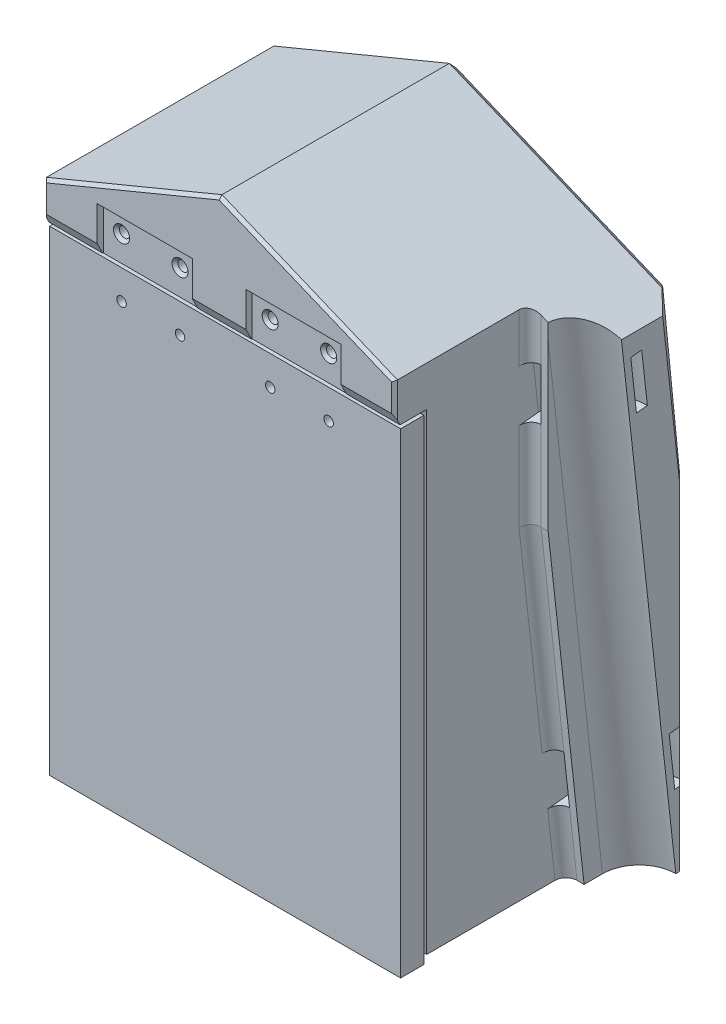
SolidWorks part; units mm, degrees
other "Door"
other "House"
other "Cover" parameters "D1"=134.3446, "D2"=7.568, "D3"=4.0473, "D4"=11.5
ref_plane "Front Plane" through (0, 0, 0) normal (0, 0, 1) x (1, 0, 0)
ref_plane "Top Plane" through (0, 0, 0) normal (0, 1, 0) x (1, 0, 0)
ref_plane "Right Plane" through (0, 0, 0) normal (1, 0, 0) x (0, 0, -1)
sketch "Sketch1" plane through (0, 0, 0) normal (0, 0, 1) x (1, 0, 0)
  line L0 (-48, 73.5589) -> (-48, -66.5589)
  line L1 (-45, -61.5589) -> (45, -61.5589)
  line L2 (-45, -61.5589) -> (-45, 61.5589)
  line L3 (-45, 61.5589) -> (45, 61.5589)
  line L4 (45, -61.5589) -> (45, 61.5589)
  line L5 (0, 61.5589) -> (0, -61.5589) construction
  line L6 (-45, 0) -> (45, 0) construction
  line L7 (-48, -66.5589) -> (48, -66.5589)
  line L8 (48, -66.5589) -> (48, 73.5589)
  line L9 (48, 73.5589) -> (0, 93.4411)
  line L10 (0, 93.4411) -> (-48, 73.5589)
  point P0 (0, 0)
  dimension "D1" = 160
  dimension "D2" = 90
  dimension "D3" = 22.5
  dimension "D4" = 12
  dimension "D5" = 5
  dimension "D6" = 3
  dimension "D7" = 123.1177
extrude "main-extrude" add sketch "Sketch1" along normal blind 60
sketch "Sketch2" plane through (0, 0, 0) normal (0, 0, 1) x (1, 0, 0)
  line L0 (48, -66.5589) -> (48, 73.5589) construction
  line L1 (-48, -66.5589) -> (48, -66.5589) construction
  line L2 (-48, 73.5589) -> (-48, -66.5589) construction
  line L3 (48, 73.5589) -> (0, 93.4411) construction
  line L4 (0, 93.4411) -> (-48, 73.5589) construction
  line L5 (48, -66.5589) -> (48, 73.5589)
  line L6 (-48, -66.5589) -> (48, -66.5589)
  line L7 (-48, 73.5589) -> (-48, -66.5589)
  line L8 (48, 73.5589) -> (0, 93.4411)
  line L9 (0, 93.4411) -> (-48, 73.5589)
extrude "rear-extrude" add sketch "Sketch2" against normal blind 5
sketch "Sketch6" plane through (0, -66.5589, 0) normal (0, -1, 0) x (1, 0, 0)
  line L0 (48, 22.9375) -> (52, 22.9375)
  line L1 (62.9375, 15) -> (62.9375, 22.9375)
  line L2 (52, 22.9375) -> (55, 22.9375)
  line L3 (-48, -5) -> (48, -5) construction
  line L4 (62.9375, 15) -> (62.9375, -5)
  line L5 (62.9375, -5) -> (48, -5)
  line L6 (48, 60) -> (48, -5) construction
  line L7 (48, -5) -> (48, 22.9375)
  line L8 (62.9375, 22.9375) -> (55, 22.9375)
  circle A0 centre (62.9375, 22.9375) radius 7.9375 construction
  arc A1 (62.9375, 15) -> (55, 22.9375) centre (62.9375, 22.9375) cw construction
  point P3 (62.9375, 15)
  dimension "D3" = 15.875
  dimension "D1" = 4
  dimension "D2" = 3
  dimension "D4" = 20
extrude "Boss-Extrude3" add sketch "Sketch6" against normal up to surface (140.1177 mm away) up to face at (24, 83.5, 27.5)
sketch "Sketch19" plane through (62.9375, 0, 0) normal (1, 0, 0) x (0, 0, -1)
  line L0 (-7.4977, -71.6348) -> (-21.3388, 52.9783) construction
  line L2 (-22.9375, 67.3716) -> (-32.8764, 66.2676) construction
  line L3 (-7.9389, -67.6628) -> (2, -66.5589) construction
  line L6 (5, -66.5589) -> (-22.9375, -66.5589) construction
  dimension "D1" = 10
  dimension "D3" = 3
ref_plane "Plane6" through (62.9375, -67.6628, 7.9389) normal (0, 0.9939, 0.1104) x (1, 0, 0)
sketch "Sketch20" plane through (62.9375, -67.6628, 7.9389) normal (0, 0.9939, 0.1104) x (1, 0, 0)
  line L0 (10, 0) -> (10, -24.5702)
  line L3 (10, -24.5702) -> (-14.9375, -24.5702)
  line L4 (21.2132, 0) -> (-21.2132, 42.4264)
  line L5 (-21.2132, 42.4264) -> (21.2132, 42.4264)
  line L6 (21.2132, 42.4264) -> (21.2132, 0)
  line L7 (0, 0) -> (10.6066, 10.6066) construction
  line L8 (-10, 0) -> (-10, -5)
  line L9 (-10, -5) -> (-14.9375, -5)
  line L10 (-14.9375, -5) -> (-14.9375, -24.5702)
  circle A0 centre (0, 0) radius 10 construction
  circle A3 centre (0, 0) radius 15 construction
  arc A4 (-10, 0) -> (10, 0) centre (0, 0) cw
  point P16 (10.6066, 10.6066)
  point P18 (10.6066, 10.6066)
  point P19 (10.6066, 10.6066)
  point P20 (10.6066, 10.6066)
  point P21 (10.6066, 10.6066)
  point P22 (7.0711, 7.0711)
  dimension "D1" = 20
  dimension "D2" = 5
  dimension "D3" = 5
extrude "Cut-Extrude9" cut sketch "Sketch20" along normal through all
ref_plane "Plane1" through (62.9375, -47.7851, 10.1468) normal (0, 0.9939, 0.1104) x (1, 0, 0)
ref_plane "Plane2" through (0, 0, 0) normal (0, 0.9939, 0.1104) x (1, 0, 0)
sketch "Sketch7" plane through (62.9375, -47.7851, 10.1468) normal (0, 0.9939, 0.1104) x (1, 0, 0)
  line L0 (-14.9375, -15) -> (-11.9375, -15)
  line L2 (-14.9375, -5) -> (-10, -5) construction
  line L4 (-11.9375, -15) -> (-11.9375, -5)
  line L5 (-11.9375, -5) -> (-11.9375, 0)
  line L6 (-14.9375, -15) -> (-14.9375, 0)
  line L7 (0, 11.9375) -> (10, 11.9375)
  line L8 (10, 11.9375) -> (10, 14.9375)
  line L9 (10, 14.9375) -> (0, 14.9375)
  line L10 (-14.9375, -51.6211) -> (-14.9375, -5) construction
  arc A2 (-11.9375, 0) -> (0, 11.9375) centre (0, 0) cw
  arc A3 (0, 14.9375) -> (-14.9375, 0) centre (0, 0) ccw
  circle A4 centre (0, 0) radius 10 construction
  dimension "D1" = 3
  dimension "D2" = 10
  dimension "D3" = 10
extrude "Cut-Extrude10" cut sketch "Sketch7" along normal blind 14
pattern_linear "LPattern1" count 2 spacing 95 along (0, 0.9939, 0.1104) of "Cut-Extrude10"
fillet "Fillet2" radius 3 4 edges at (48, 67.0117, 22.9375) (48, 34.2288, 22.9375) (48, -57.4479, 14.1042) (48, -6.1717, 19.7996)
sketch "Sketch9" plane through (0, -66.5589, 0) normal (0, -1, 0) x (1, 0, 0)
  line L0 (-48, 0) -> (48, 0) construction
  line L3 (-30, 3) -> (0, 3) construction
  line L4 (0, 3) -> (30, 3) construction
  circle A0 centre (-30, 3) radius 3
  circle A1 centre (0, 3) radius 3
  circle A2 centre (30, 3) radius 3
  dimension "D1" = 6
  dimension "D2" = 30
extrude "inner-drain-holes" cut sketch "Sketch9" against normal blind 15
sketch "Sketch4" plane through (0, 0, 60) normal (0, 0, 1) x (1, 0, 0)
  line L0 (-48, 73.5589) -> (-48, -66.5589) construction
  line L1 (-48, 61.5589) -> (48, 61.5589) construction
  line L2 (-48, 61.5589) -> (-48, -66.5589)
  line L3 (-48, -66.5589) -> (48, -66.5589)
  line L4 (48, 61.5589) -> (48, -66.5589)
  line L5 (48, -66.5589) -> (48, 73.5589) construction
  line L6 (-48, 61.5589) -> (-48, 62.5589)
  line L7 (-48, 73.5589) -> (-48, -66.5589) construction
  line L8 (-48, 62.5589) -> (48, 62.5589)
  line L9 (48, -66.5589) -> (48, 73.5589) construction
  line L10 (48, 62.5589) -> (48, 61.5589)
  dimension "D1" = 1
extrude "Cut-Extrude2" cut sketch "Sketch4" against normal blind 8
sketch "Sketch5" plane through (0, 0, 60) normal (0, 0, 1) x (1, 0, 0)
  line L0 (-33.3333, 61.5589) -> (-7.3333, 61.5589) construction
  line L1 (-33.3333, 48.0589) -> (-7.3333, 48.0589)
  line L2 (-33.3333, 48.0589) -> (-33.3333, 75.0589)
  line L3 (-33.3333, 75.0589) -> (-7.3333, 75.0589)
  line L4 (-7.3333, 48.0589) -> (-7.3333, 75.0589)
  line L5 (-20.3333, 75.0589) -> (-20.3333, 48.0589) construction
  line L6 (-33.3333, 61.5589) -> (-7.3333, 61.5589) construction
  line L7 (-45, 61.5589) -> (45, 61.5589) construction
  line L8 (-48, 61.5589) -> (48, 61.5589) construction
  line L9 (0, -987.8214) -> (0, 49012.1786) construction
  line L10 (-33.3333, 61.5589) -> (-48, 61.5589) construction
  line L11 (-48, 73.5589) -> (-48, -66.5589) construction
  line L12 (33.3333, 75.0589) -> (7.3333, 75.0589)
  line L13 (7.3333, 48.0589) -> (7.3333, 75.0589)
  line L14 (33.3333, 48.0589) -> (7.3333, 48.0589)
  line L15 (33.3333, 48.0589) -> (33.3333, 75.0589)
  line L16 (-7.3333, 61.5589) -> (7.3333, 61.5589) construction
  point P0 (-20.3333, 61.5589)
  dimension "D1" = 27
  dimension "D2" = 26
extrude "Cut-Extrude3" cut sketch "Sketch5" against normal offset from surface (1.65 mm away) 6.35 up to face at (0, 0, 52)
sketch "Sketch15" plane through (0, 0, 58.35) normal (0, 0, 1) x (1, 0, 0)
  line L0 (-28.3333, 69.5589) -> (-12.3333, 69.5589) construction
  line L1 (0, -934.1648) -> (0, 49065.8352) construction
  line L2 (0, -200987.8214) -> (0, 249012.1786) construction
  line L3 (-20.3333, 75.0589) -> (-20.3333, 48.0589) construction
  line L4 (-33.3333, 61.5589) -> (-7.3333, 61.5589) construction
  circle A0 centre (-28.3333, 69.5589) radius 1.4
  circle A1 centre (-12.3333, 69.5589) radius 1.4
  circle A2 centre (28.3333, 69.5589) radius 1.4
  circle A3 centre (12.3333, 69.5589) radius 1.4
  point P8 (-20.3333, 69.5589)
  dimension "D1" = 2.8
  dimension "D2" = 16
  dimension "D3" = 8
extrude "Cut-Extrude7" cut sketch "Sketch15" against normal blind 40
sketch "Sketch12" plane through (0, 0, 52) normal (0, 0, 1) x (1, 0, 0)
  line L5 (0, 61.5589) -> (0, -61.5589) construction
  line L6 (-48.001, 61.5589) -> (48.001, 61.5589)
  line L7 (-48.001, 61.5589) -> (-48.001, -68.5589)
  line L8 (-48.001, -68.5589) -> (48.001, -68.5589)
  line L9 (48.001, 61.5589) -> (48.001, -68.5589)
  line L10 (0, -68.5589) -> (0, 61.5589) construction
  line L11 (-48.001, -3.5) -> (48.001, -3.5) construction
  line L12 (-48, -66.5589) -> (48, -66.5589) construction
  line L13 (-48, 73.5589) -> (-48, -66.5589) construction
  point P0 (0, -3.5)
  dimension "D1" = 2
  dimension "D2" = 0.001
extrude "Boss-Extrude5" add sketch "Sketch12" along normal blind 6.35 separate body
sketch "Sketch13" plane through (0, 0, 58.35) normal (0, 0, 1) x (1, 0, 0)
  line L0 (-1053.3426, 61.5589) -> (48946.6574, 61.5589) construction
  line L1 (-33.3333, 61.5589) -> (-48, 61.5589) construction
  line L4 (7.3333, 48.0589) -> (33.3333, 48.0589)
  line L5 (33.3333, 48.0589) -> (33.3333, 75.0589)
  line L6 (33.3333, 75.0589) -> (7.3333, 75.0589)
  line L7 (7.3333, 75.0589) -> (7.3333, 48.0589)
  line L8 (7.3333, 48.0589) -> (33.3333, 48.0589) construction
  line L9 (33.3333, 48.0589) -> (33.3333, 75.0589) construction
  line L10 (33.3333, 75.0589) -> (7.3333, 75.0589) construction
  line L11 (7.3333, 75.0589) -> (7.3333, 48.0589) construction
  line L12 (-33.3333, 48.0589) -> (-7.3333, 48.0589)
  line L13 (-33.3333, 75.0589) -> (-33.3333, 48.0589)
  line L14 (-7.3333, 75.0589) -> (-33.3333, 75.0589)
  line L15 (-7.3333, 48.0589) -> (-7.3333, 75.0589)
  line L16 (-33.3333, 48.0589) -> (-7.3333, 48.0589) construction
  line L17 (-33.3333, 75.0589) -> (-33.3333, 48.0589) construction
  line L18 (-7.3333, 75.0589) -> (-33.3333, 75.0589) construction
  line L19 (-7.3333, 48.0589) -> (-7.3333, 75.0589) construction
  circle A0 centre (28.3333, 69.5589) radius 1.4 construction
  circle A1 centre (12.3333, 69.5589) radius 1.4 construction
  circle A2 centre (-28.3333, 69.5589) radius 1.4 construction
  circle A3 centre (-12.3333, 69.5589) radius 1.4 construction
  circle A4 centre (28.3333, 69.5589) radius 1.4 construction
  circle A5 centre (12.3333, 69.5589) radius 1.4 construction
  circle A6 centre (-28.3333, 69.5589) radius 1.4 construction
  circle A7 centre (-12.3333, 69.5589) radius 1.4 construction
  circle A8 centre (28.3333, 53.5589) radius 1.4 construction
  circle A9 centre (12.3333, 53.5589) radius 1.4 construction
  circle A10 centre (-12.3333, 53.5589) radius 1.4 construction
  circle A11 centre (-28.3333, 53.5589) radius 1.4 construction
  circle A12 centre (-28.3333, 53.5589) radius 1.3
  circle A13 centre (-12.3333, 53.5589) radius 1.3
  circle A14 centre (12.3333, 53.5589) radius 1.3
  circle A15 centre (28.3333, 53.5589) radius 1.3
  dimension "D3" = 2.6
  dimension "D1" = 0
  dimension "D2" = 0
extrude "Cut-Extrude8" cut sketch "Sketch13" against normal through all
chamfer "Chamfer4" distance 3 distance2 1.5 3 edges at (0, 62.5589, 60) (-40.6667, 62.5589, 60) (40.6667, 62.5589, 60) first distance on face at (0, 70.4729, 60)
chamfer "Chamfer7" distance 0.8 angle 45 4 edges at (26.9333, 69.5589, 58.35) (10.9333, 69.5589, 58.35) (-10.9333, 69.5589, 58.35) (-26.9333, 69.5589, 58.35)
fillet "cavity-fillet" radius 5 4 edges at (45, -61.5589, 26) (-45, -61.5589, 26) (45, 61.5589, 26) (-45, 61.5589, 26)
sketch "Sketch21" plane through (0, 0, 0) normal (0, 0, 1) x (1, 0, 0)
  line L14 (30, -61.0589) -> (40, -61.0589)
  line L15 (44.5, -56.5589) -> (44.5, 56.5589)
  line L16 (40, 61.0589) -> (-40, 61.0589)
  line L17 (-44.5, 56.5589) -> (-44.5, -56.5589)
  line L18 (-40, -61.0589) -> (-30, -61.0589)
  line L19 (-30, -61.0589) -> (0, -61.0589)
  line L20 (0, -61.0589) -> (30, -61.0589)
  line L21 (30, -61.0589) -> (40, -61.0589)
  line L22 (44.5, -56.5589) -> (44.5, 56.5589)
  line L23 (40, 61.0589) -> (-40, 61.0589)
  line L24 (-44.5, 56.5589) -> (-44.5, -56.5589)
  line L25 (-40, -61.0589) -> (-30, -61.0589)
  line L26 (-30, -61.0589) -> (0, -61.0589)
  line L27 (0, -61.0589) -> (30, -61.0589)
  circle A4 centre (-38.5, 55.0589) radius 6 construction
  circle A5 centre (38.5, 55.0589) radius 6 construction
  circle A6 centre (38.5, -55.0589) radius 6 construction
  circle A7 centre (-38.5, -55.0589) radius 6 construction
  arc A8 (40, -61.0589) -> (44.5, -56.5589) centre (40, -56.5589) ccw
  arc A9 (44.5, 56.5589) -> (40, 61.0589) centre (40, 56.5589) ccw
  arc A10 (-40, 61.0589) -> (-44.5, 56.5589) centre (-40, 56.5589) ccw
  arc A11 (-44.5, -56.5589) -> (-40, -61.0589) centre (-40, -56.5589) ccw
  arc A12 (40, -61.0589) -> (44.5, -56.5589) centre (40, -56.5589) ccw
  arc A13 (44.5, 56.5589) -> (40, 61.0589) centre (40, 56.5589) ccw
  arc A14 (-40, 61.0589) -> (-44.5, 56.5589) centre (-40, 56.5589) ccw
  arc A15 (-44.5, -56.5589) -> (-40, -61.0589) centre (-40, -56.5589) ccw
  circle A17 centre (-38.5, 55.0589) radius 1.3
  circle A18 centre (38.5, 55.0589) radius 1.3
  circle A19 centre (-38.5, -55.0589) radius 1.3
  circle A20 centre (38.5, -55.0589) radius 1.3
  dimension "D2" = 12
  dimension "D5" = 2.6
  dimension "D1" = 0.5
  dimension "D3" = 2
  dimension "D4" = 2
extrude "Boss-Extrude10" add sketch "Sketch21" along normal blind 3 separate body
sketch "Sketch22" plane through (0, 0, 0) normal (0, 0, 1) x (1, 0, 0)
  circle A0 centre (-38.5, 55.0589) radius 2
  circle A1 centre (38.5, 55.0589) radius 2
  circle A2 centre (-38.5, -55.0589) radius 2
  circle A3 centre (38.5, -55.0589) radius 2
  circle A4 centre (-38.5, 55.0589) radius 1.3 construction
  circle A5 centre (38.5, 55.0589) radius 1.3 construction
  circle A6 centre (38.5, -55.0589) radius 1.3 construction
  circle A7 centre (-38.5, -55.0589) radius 1.3 construction
  dimension "D1" = 4
extrude "Cut-Extrude11" cut sketch "Sketch22" against normal through all
chamfer "Chamfer6" distance 0.8 angle 45 11 edges at (-45, 0, 52) (-43.5355, 60.0944, 52) (-43.5355, -60.0944, 52) (0, 61.5589, 52) (0, -61.5589, 52) (43.5355, 60.0944, 52) (43.5355, -60.0944, 52) (45, 0, 52) (-48, -2, 52) (48, -2, 52) (0, -66.5589, 52)
chamfer "Chamfer2" distance 2 angle 45 5 edges at (62.9375, -29.2762, -5) (7.4687, -66.5589, -5) (-48, 3.5, -5) (28.035, 81.8287, -5) (-24, 83.5, -5)
chamfer "Chamfer9" distance 0.8 angle 45 4 edges at (-48, 69.5589, 60) (48, 69.5589, 60) (24, 83.5, 60) (-24, 83.5, 60)
equation "\"D1@Sketch19\"=\"D4@Sketch6\"/2"
